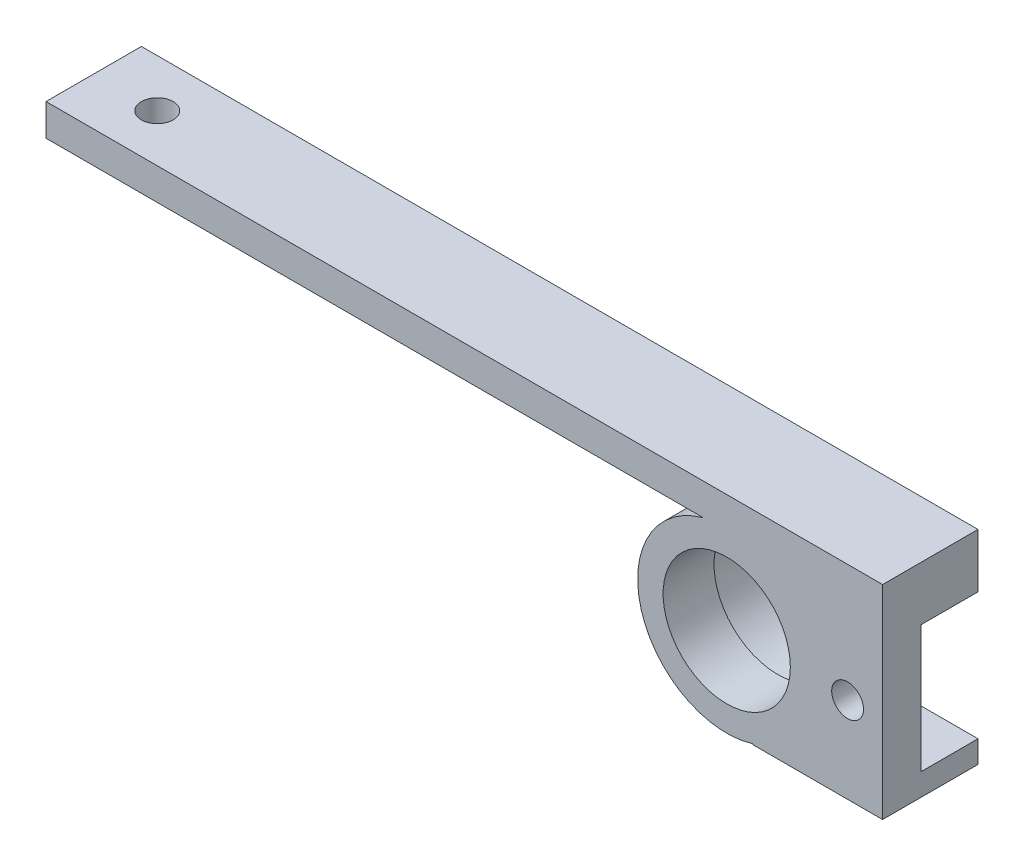
SolidWorks part; units mm, degrees
ref_plane "前视基准面" through (0, 0, 0) normal (0, 0, 1) x (1, 0, 0)
ref_plane "上视基准面" through (0, 0, 0) normal (0, 1, 0) x (1, 0, 0)
ref_plane "右视基准面" through (0, 0, 0) normal (1, 0, 0) x (0, 0, -1)
sketch "草图1" plane through (0, 0, 0) normal (0, 0, 1) x (1, 0, 0)
  line L1 (20, -10) -> (-20, -10)
  line L2 (20, -10) -> (20, 10)
  line L3 (20, 10) -> (-20, 10)
  line L4 (-20, -10) -> (-20, 10)
  line L5 (20, -10) -> (-20, 10) construction
  line L6 (20, 10) -> (-20, -10) construction
  point P0 (0, 0)
  dimension "D1" = 40
  dimension "D2" = 20
extrude "凸台-拉伸1" add sketch "草图1" along normal blind 6
sketch "草图2" plane through (0, 0, 6) normal (0, 0, 1) x (1, 0, 0)
  line L0 (20, -10) -> (20, 10) construction
  circle A0 centre (10, 0) radius 2.5
  circle A1 centre (-1, 0) radius 2.5
  circle A2 centre (-12, 0) radius 2.5
  dimension "D1" = 10
  dimension "D2" = 5
  dimension "D3" = 3
extrude "切除-拉伸1" cut sketch "草图2" against normal through all
sketch "草图3" plane through (0, 0, 6) normal (0, 0, 1) x (1, 0, 0)
  line L0 (20, 13.5) -> (20, 10)
  line L1 (20, -13.5) -> (-26.894, -13.5)
  line L3 (20, 13.5) -> (-26.894, 13.5)
  line L4 (-20, 10) -> (-20, -10)
  line L5 (-20, -10) -> (20, -10)
  line L6 (20, -10) -> (20, 10)
  line L7 (20, 10) -> (-20, 10)
  line L8 (-20, 10) -> (-20, -10)
  line L9 (-20, -10) -> (20, -10)
  line L10 (20, -10) -> (20, 10)
  line L11 (20, 10) -> (-20, 10)
  line L12 (-26.894, -13.5) -> (-26.894, 13.5)
  line L13 (20, -10.0394) -> (-26.894, 13.5) construction
  line L14 (20, 10.0394) -> (-26.894, -13.5) construction
  line L15 (20, -10) -> (20, -13.5)
  circle A0 centre (-31, 0) radius 11
  circle A1 centre (-31, 0) radius 14
  point P2 (0, 0)
  line M10 (-20, 10) -> (-20, -10)
  line M11 (-20, -10) -> (20, -10)
  line M13 (20, 10) -> (-20, 10)
  dimension "D3" = 22
  dimension "D4" = 28
  dimension "D2" = 3.5
  dimension "D1" = 0
extrude "凸台-拉伸2" add sketch "草图3" against normal blind 15 contours L3 A1 L1 L12 A0 | A1 L1 L15 M11 M10 | L1 A1 L8 A0 L12 | L8 A1 L3 L12 A0 | L8 A1 | A1 L0 L3 M10 M13 region at (-1.9449, 11.7771, 6) region at (-1.9449, -11.7771, 6) region at (-23.0173, 9.0328, 6) region at (-27.2274, 11.7946, 6) region at (-18.7882, 0, 6) region at (-23.0173, -9.0328, 6)
sketch "草图5" plane through (0, 0, 6) normal (0, 0, 1) x (1, 0, 0)
  circle A0 centre (-31, 0) radius 10
  circle A1 centre (-31, 0) radius 11 construction
  circle A2 centre (-31, 0) radius 11
  dimension "D1" = 20
extrude "凸台-拉伸3" add sketch "草图5" against normal blind 8
sketch "草图6" plane through (0, 0, 6) normal (0, 0, 1) x (1, 0, 0)
  circle A0 centre (-31, 0) radius 8.5
  circle A1 centre (-31, 0) radius 10 construction
  circle A2 centre (-31, 0) radius 10
  dimension "D1" = 17
sketch "草图7" plane through (0, 13.5, 0) normal (0, 1, 0) x (1, 0, 0)
  circle A0 centre (-17.1666, 1.953) radius 2.6594
sketch "草图8" plane through (20, 0, 0) normal (1, 0, 0) x (0, 0, -1)
  line L1 (-6, 13.5) -> (9, 13.5)
  line L2 (-6, 13.5) -> (-6, 18.5)
  line L3 (-6, 18.5) -> (9, 18.5)
  line L4 (9, 13.5) -> (9, 18.5)
  dimension "D1" = 5
extrude "凸台-拉伸4" add sketch "草图8" against normal blind 500
sketch "草图9" plane through (0, 0, -9) normal (0, 0, -1) x (-1, 0, 0)
  line L1 (24.4567, 15.8334) -> (28.494, 15.8334)
  line L2 (24.4567, 15.8334) -> (24.4567, 12.469)
  line L3 (24.4567, 12.469) -> (28.494, 12.469)
  line L4 (28.494, 15.8334) -> (28.494, 12.469)
extrude "凸台-拉伸5" add sketch "草图9" against normal through all
sketch "草图10" plane through (0, 0, 6) normal (0, 0, 1) x (1, 0, 0)
  line L0 (-12, 0) -> (-1, 0) construction
  line L1 (-6.5, 0) -> (-6.5, 18.5) construction
  line L2 (-480, 18.5) -> (20, 18.5) construction
  line L4 (-6.5, 18.5) -> (20, 18.5)
  line L5 (-6.5, 18.5) -> (-6.5, -13.5)
  line L6 (-6.5, -13.5) -> (20, -13.5)
  line L7 (20, 18.5) -> (20, -13.5)
extrude "切除-拉伸2" cut sketch "草图10" against normal through all
sketch "草图11" plane through (0, 18.5, 0) normal (0, 1, 0) x (1, 0, 0)
  line L0 (-138.0156, 9) -> (-138.0156, -6.0139)
  line L1 (-480, 9) -> (-6.5, 9) construction
  line L2 (-138.0156, 260.8283) -> (-138.0156, -109.1717) construction
sketch "草图12" plane through (0, 18.5, 0) normal (0, 1, 0) x (1, 0, 0)
  line L1 (-138.0156, -6.0139) -> (-501.7351, -6.0139)
  line L2 (-138.0156, -6.0139) -> (-138.0156, 21.5219)
  line L3 (-138.0156, 21.5219) -> (-501.7351, 21.5219)
  line L4 (-501.7351, -6.0139) -> (-501.7351, 21.5219)
extrude "切除-拉伸3" cut sketch "草图12" against normal through all
sketch "草图13" plane through (0, 18.5, 0) normal (0, 1, 0) x (1, 0, 0)
  line L0 (-138.0156, 1.493) -> (-128.0156, 1.493) construction
  line L1 (-138.0156, 9) -> (-138.0156, -6.0139) construction
  circle A0 centre (-128.0156, 1.493) radius 2.5
  dimension "D2" = 5
  dimension "D1" = 10
extrude "切除-拉伸4" cut sketch "草图13" against normal blind 10
